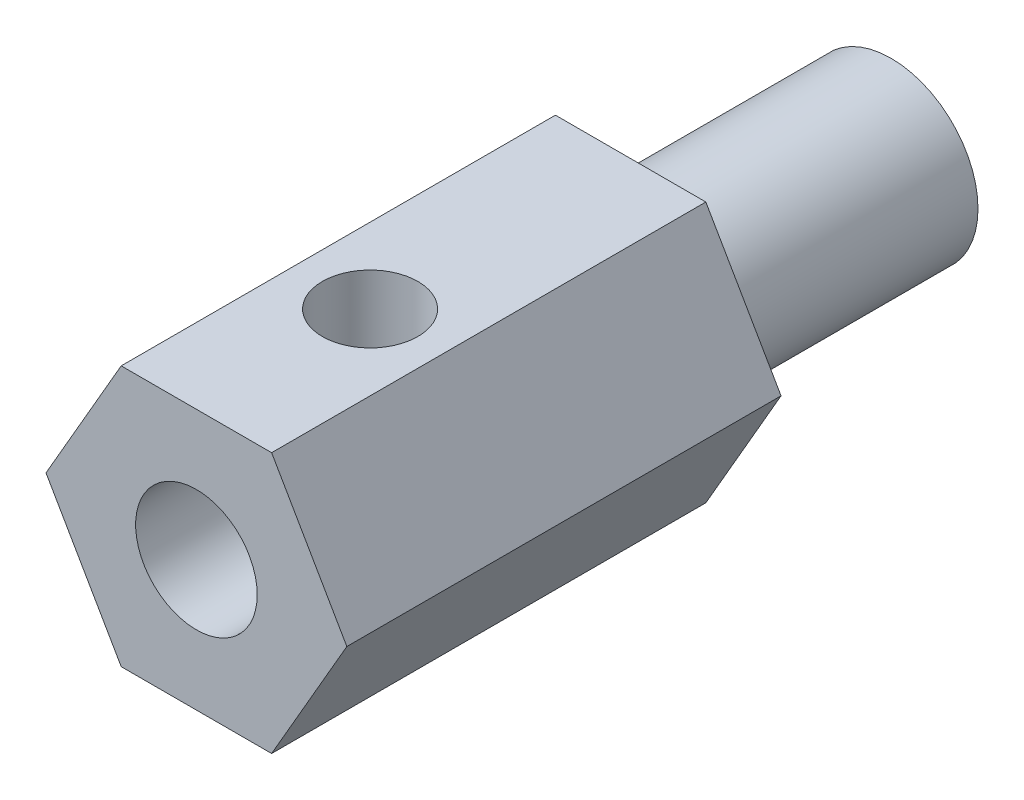
SolidWorks part; units mm, degrees
ref_plane "Front Plane" through (0, 0, 0) normal (0, 0, 1) x (1, 0, 0)
ref_plane "Top Plane" through (0, 0, 0) normal (0, 1, 0) x (1, 0, 0)
ref_plane "Right Plane" through (0, 0, 0) normal (1, 0, 0) x (0, 0, -1)
sketch "Sketch1" plane through (0, 0, 0) normal (0, 0, 1) x (1, 0, 0)
  line L1 (2.1997, 3.81) -> (-2.1997, 3.81)
  line L2 (-2.1997, 3.81) -> (-4.3994, 0)
  line L3 (-4.3994, 0) -> (-2.1997, -3.81)
  line L4 (-2.1997, -3.81) -> (2.1997, -3.81)
  line L5 (2.1997, -3.81) -> (4.3994, 0)
  line L6 (4.3994, 0) -> (2.1997, 3.81)
  circle A0 centre (0, 0) radius 3.81 construction
  dimension "D1" = 7.62
extrude "Boss-Extrude1" add sketch "Sketch1" along normal blind 25.4
sketch "Sketch2" plane through (0, 0, 25.4) normal (0, 0, 1) x (1, 0, 0)
  line L0 (-1.4591, 1.016) -> (1.4591, 1.016)
  line L1 (0, 1.016) -> (0, -1.778) construction
  circle A0 centre (0, 0) radius 1.778
  dimension "D1" = 3.556
  dimension "D2" = 2.794
extrude "Cut-Extrude1" cut sketch "Sketch2" against normal blind 8.89 contours L1 L0 A0 | L0 L1 A0 region at (-0.7896, -0.2474, 25.4) region at (0.7896, -0.2474, 25.4)
extrude "Cut-Extrude2" cut sketch "Sketch2<3>" against normal blind 2.54 contours A0
sketch "Sketch2<3>" plane through (0, 0, 25.4) normal (0, 0, 1) x (1, 0, 0) same geometry as "Sketch2"
sketch "Sketch6" plane through (0, 0, 0) normal (0, 0, -1) x (-1, 0, 0)
  circle A0 centre (0, 0) radius 1.524
  dimension "D1" = 3.048
extrude "Cut-Extrude3" cut sketch "Sketch6" against normal up to surface (16.51 mm away) up to face at (0, -0.381, 16.51)
sketch "Sketch7" plane through (0, 3.81, 0) normal (0, 1, 0) x (1, 0, 0)
  line L0 (2.1997, -25.4) -> (-2.1997, -25.4) construction
  circle A0 centre (0, -20.32) radius 1.397
  dimension "D1" = 2.794
  dimension "D2" = 5.08
extrude "Cut-Extrude4" cut sketch "Sketch7" against normal blind 3.81
sketch "Sketch8" plane through (0, 0, 0) normal (0, 0, -1) x (-1, 0, 0)
  line L1 (-6.7915, 6.1771) -> (6.0059, 6.1771)
  line L2 (-6.7915, 6.1771) -> (-6.7915, -5.9568)
  line L3 (-6.7915, -5.9568) -> (6.0059, -5.9568)
  line L4 (6.0059, 6.1771) -> (6.0059, -5.9568)
extrude "Cut-Extrude5" cut sketch "Sketch8" against normal blind 5.08
sketch "Sketch9" plane through (0, 0, 5.08) normal (0, 0, -1) x (-1, 0, 0)
  circle A0 centre (0, 0) radius 2.54
  circle A1 centre (0, 0) radius 5.4478
  dimension "D1" = 5.08
extrude "Cut-Extrude6" cut sketch "Sketch9" against normal blind 7.62
